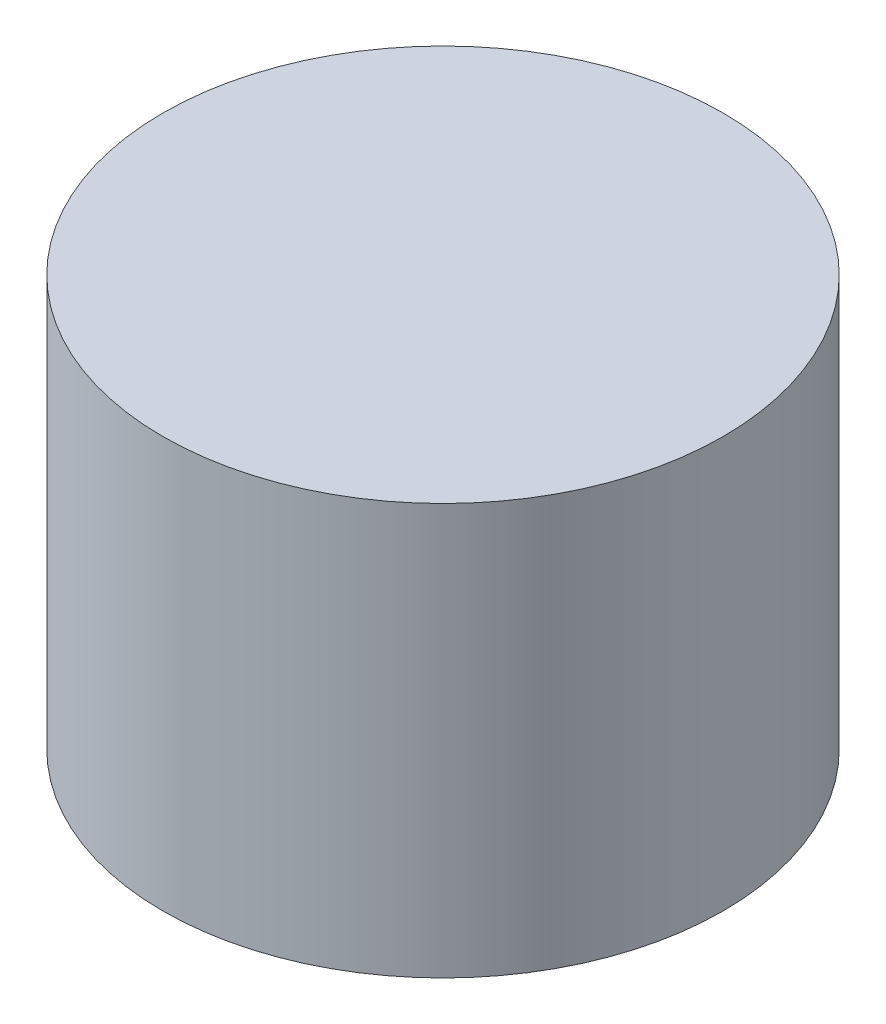
SolidWorks part; units mm, degrees
material "AISI 1035 Acciaio (SS)"
ref_plane "Piano frontale" through (0, 0, 0) normal (0, 0, 1) x (1, 0, 0)
ref_plane "Piano superiore" through (0, 0, 0) normal (0, 1, 0) x (1, 0, 0)
ref_plane "Piano destro" through (0, 0, 0) normal (1, 0, 0) x (0, 0, -1)
sketch "Schizzo1" plane through (0, 0, 0) normal (0, 0, 1) x (1, 0, 0)
  line L0 (-12, 0) -> (-12, 16)
  line L1 (-12, 16) -> (0, 16)
  line L2 (0, 16) -> (0, 22)
  line L3 (0, 22) -> (-15, 22)
  line L4 (-15, 22) -> (-15, 0)
  line L5 (-15, 0) -> (-12, 0)
  line L6 (0, 0) -> (0, 29.0615) construction
  dimension "D1" = 30
  dimension "D2" = 24
  dimension "D3" = 22
  dimension "D4" = 16
revolve "Rivoluzione1" add sketch "Schizzo1" angle 360 about L6
